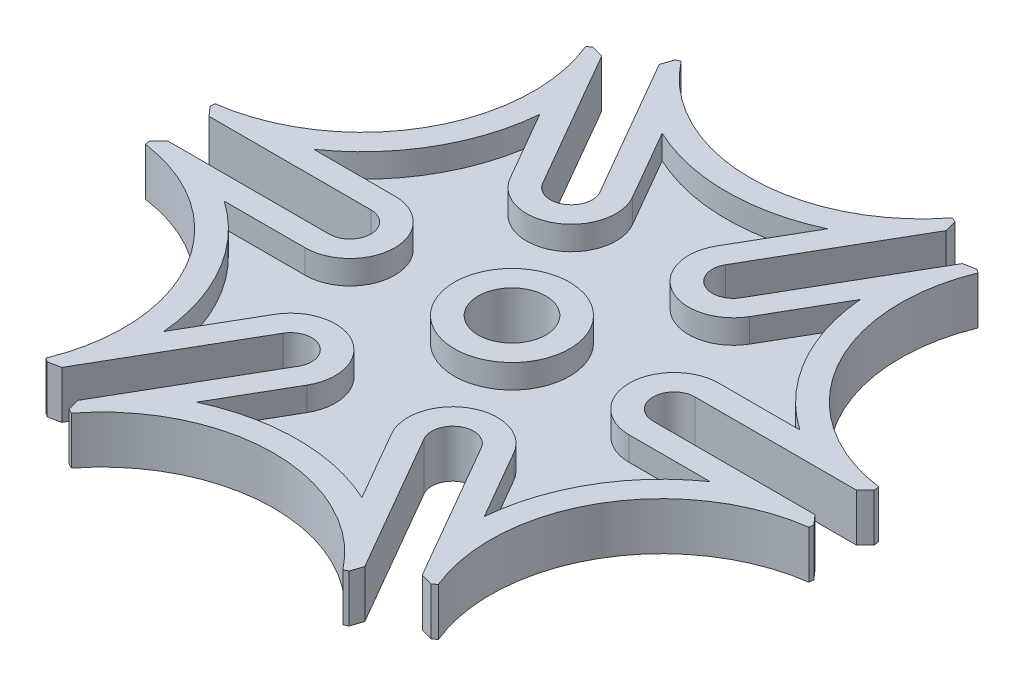
SolidWorks part; units mm, degrees
material "Brass"
ref_plane "Front Plane" through (0, 0, 0) normal (0, 0, 1) x (1, 0, 0)
ref_plane "Top Plane" through (0, 0, 0) normal (0, 1, 0) x (1, 0, 0)
ref_plane "Right Plane" through (0, 0, 0) normal (1, 0, 0) x (0, 0, -1)
sketch "Sketch1" plane through (0, 0, 0) normal (0, 1, 0) x (1, 0, 0)
  line L0 (0, 0) -> (44.45, 0) construction
  line L1 (0, 0) -> (22.225, 38.4948) construction
  line L3 (13.2147, 17.3005) -> (24.6007, 37.0217)
  line L4 (21.59, 2.794) -> (44.3621, 2.794)
  line L5 (13.2147, -17.3005) -> (24.6007, -37.0217)
  line L6 (21.59, -2.794) -> (44.3621, -2.794)
  line L7 (-8.3753, -20.0945) -> (-19.7614, -39.8157)
  line L8 (8.3753, -20.0945) -> (19.7614, -39.8157)
  line L9 (-21.59, -2.794) -> (-44.3621, -2.794)
  line L10 (-13.2147, -17.3005) -> (-24.6007, -37.0217)
  line L11 (-13.2147, 17.3005) -> (-24.6007, 37.0217)
  line L12 (-21.59, 2.794) -> (-44.3621, 2.794)
  line L13 (8.3753, 20.0945) -> (19.7614, 39.8157)
  line L14 (-8.3753, 20.0945) -> (-19.7614, 39.8157)
  line L15 (0, 0) -> (47.2936, -27.305) construction
  circle A0 centre (0, 0) radius 4.5085
  arc A2 (44.3621, 2.794) -> (44.2056, 4.6545) centre (0, 0) ccw
  arc A3 (9.398, 16.2778) -> (13.2147, 17.3005) centre (10.795, 18.6975) ccw
  arc A4 (21.59, 2.794) -> (18.796, 0) centre (21.59, 0) ccw
  arc A5 (26.1338, 35.9559) -> (44.2056, 4.6545) centre (47.2936, 27.305) ccw
  arc A6 (26.1338, 35.9559) -> (24.6007, 37.0217) centre (0, 0) ccw
  arc A7 (13.2147, -17.3005) -> (9.398, -16.2778) centre (10.795, -18.6975) ccw
  arc A8 (44.2056, -4.6545) -> (26.1338, -35.9559) centre (47.2936, -27.305) ccw
  arc A9 (18.796, 0) -> (21.59, -2.794) centre (21.59, 0) ccw
  arc A10 (24.6007, -37.0217) -> (26.1338, -35.9559) centre (0, 0) ccw
  arc A11 (44.2056, -4.6545) -> (44.3621, -2.794) centre (0, 0) ccw
  arc A12 (-8.3753, -20.0945) -> (-9.398, -16.2778) centre (-10.795, -18.6975) ccw
  arc A13 (18.0719, -40.6105) -> (-18.0719, -40.6105) centre (0, -54.61) ccw
  arc A14 (9.398, -16.2778) -> (8.3753, -20.0945) centre (10.795, -18.6975) ccw
  arc A15 (-19.7614, -39.8157) -> (-18.0719, -40.6105) centre (0, 0) ccw
  arc A16 (18.0719, -40.6105) -> (19.7614, -39.8157) centre (0, 0) ccw
  arc A17 (-21.59, -2.794) -> (-18.796, 0) centre (-21.59, 0) ccw
  arc A18 (-26.1338, -35.9559) -> (-44.2056, -4.6545) centre (-47.2936, -27.305) ccw
  arc A19 (-9.398, -16.2778) -> (-13.2147, -17.3005) centre (-10.795, -18.6975) ccw
  arc A20 (-44.3621, -2.794) -> (-44.2056, -4.6545) centre (0, 0) ccw
  arc A21 (-26.1338, -35.9559) -> (-24.6007, -37.0217) centre (0, 0) ccw
  arc A22 (-13.2147, 17.3005) -> (-9.398, 16.2778) centre (-10.795, 18.6975) ccw
  arc A23 (-44.2056, 4.6545) -> (-26.1338, 35.9559) centre (-47.2936, 27.305) ccw
  arc A24 (-18.796, 0) -> (-21.59, 2.794) centre (-21.59, 0) ccw
  arc A25 (-24.6007, 37.0217) -> (-26.1338, 35.9559) centre (0, 0) ccw
  arc A26 (-44.2056, 4.6545) -> (-44.3621, 2.794) centre (0, 0) ccw
  arc A27 (8.3753, 20.0945) -> (9.398, 16.2778) centre (10.795, 18.6975) ccw
  arc A28 (-18.0719, 40.6105) -> (18.0719, 40.6105) centre (0, 54.61) ccw
  arc A29 (-9.398, 16.2778) -> (-8.3753, 20.0945) centre (-10.795, 18.6975) ccw
  arc A30 (19.7614, 39.8157) -> (18.0719, 40.6105) centre (0, 0) ccw
  arc A31 (-18.0719, 40.6105) -> (-19.7614, 39.8157) centre (0, 0) ccw
  point P18 (26.1338, 35.9559)
  point P19 (44.2056, 4.6545)
  point P75 (0, 0)
  dimension "D1" = 9.017
  dimension "D2" = 88.9
  dimension "D4" = 5.588
  dimension "D5" = 21.59
  dimension "D6" = 5.588
  dimension "D8" = 54.61
  dimension "D10" = 22.86
  dimension "D3" = 60
  dimension "D7" = 21.59
  dimension "D9" = 30
  dimension "D11" = 6
extrude "Boss-Extrude1" add sketch "Sketch1" along normal blind 6.35 contours A28 A31 L14 A29 A22 L11 A25 A23 A26 L12 A24 A17 L9 A20 A18 A21 L10 A19 A12 L7 A15 A13 A16 L8 A14 A7 L5 A10 A8 A11 L6 A9 A4 L4 A2 A5 A6 L3 A3 A27 L13 A30 A0 region at (19.9494, 0, -26.5597)
chamfer "Chamfer1" distance 1.27 angle 45 12 edges at (44.3621, 3.175, 2.794) (44.3621, 3.175, -2.794) (24.6007, 3.175, -37.0217) (19.7614, 3.175, -39.8157) (-19.7614, 3.175, -39.8157) (-24.6007, 3.175, -37.0217) (-44.3621, 3.175, -2.794) (-44.3621, 3.175, 2.794) (-24.6007, 3.175, 37.0217) (-19.7614, 3.175, 39.8157) (19.7614, 3.175, 39.8157) (24.6007, 3.175, 37.0217) first distance on face at (44.2888, 3.175, 3.7247) first distance on face at (32.9761, 3.175, -2.794) first distance on face at (25.37, 3.175, -36.4928) first distance on face at (14.0684, 3.175, -29.9551) first distance on face at (-18.9187, 3.175, -40.2175) first distance on face at (-18.9077, 3.175, -27.1611) first distance on face at (-44.2888, 3.175, -3.7247) first distance on face at (-32.9761, 3.175, 2.794) first distance on face at (-25.37, 3.175, 36.4928) first distance on face at (-14.0684, 3.175, 29.9551) first distance on face at (18.9187, 3.175, 40.2175) first distance on face at (18.9077, 3.175, 27.1611)
shell "Shell3" thickness 3.175 removed face at (0, 6.35, 4.5085)
sketch "Sketch4" plane through (0, 0, 0) normal (0, -1, 0) x (1, 0, 0)
  circle A0 centre (0, 0) radius 9.525
  circle A1 centre (0, 0) radius 4.5085 construction
  circle A2 centre (0, 0) radius 4.5085
  dimension "D1" = 19.05
extrude "Boss-Extrude2" add sketch "Sketch4" along normal blind 6.604
